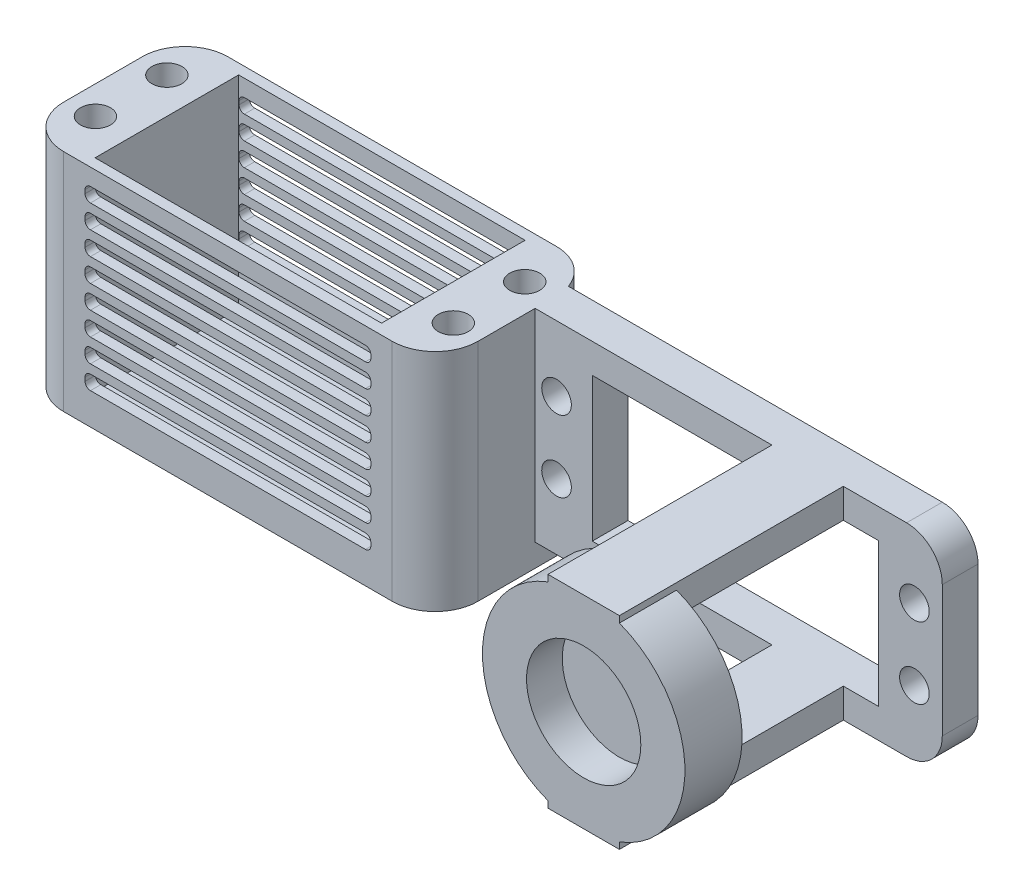
SolidWorks part; units mm, degrees
ref_plane "Front Plane" through (0, 0, 0) normal (0, 0, 1) x (1, 0, 0)
ref_plane "Top Plane" through (0, 0, 0) normal (0, 1, 0) x (1, 0, 0)
ref_plane "Right Plane" through (0, 0, 0) normal (1, 0, 0) x (0, 0, -1)
sketch "Sketch1" plane through (0, 0, 0) normal (0, 1, 0) x (1, 0, 0)
  line L0 (9.9, 0.4273) -> (50, 0.4273)
  line L1 (50, 0.4273) -> (50, -19.6727)
  line L2 (50, -19.6727) -> (9.9, -19.6727)
  line L4 (0.95, -21.1227) -> (58.95, -21.1227)
  line L5 (58.95, -21.1227) -> (58.95, 1.8773)
  line L6 (58.95, 1.8773) -> (0.95, 1.8773)
  line L8 (55, -4.6227) -> (55, -14.6227) construction
  line L9 (0.95, 1.8773) -> (0.95, -21.1227)
  line L10 (9.9, 0.4273) -> (9.9, -19.6727)
  line L11 (29.95, 0.4273) -> (29.95, -19.6727) construction
  circle A0 centre (55, -4.6227) radius 2.1
  circle A1 centre (55, -14.6227) radius 2.1
  circle A2 centre (4.9, -14.6227) radius 2.1
  circle A3 centre (4.9, -4.6227) radius 2.1
  point P13 (55, -9.6227)
  point P14 (50, -9.6227)
  point P20 (0.95, -9.6227)
  point P22 (29.95, 1.8773)
  dimension "D1" = 4.2
  dimension "D2" = 10
  dimension "D3" = 23
  dimension "D4" = 40.1
  dimension "D5" = 5
  dimension "D6" = 20.1
  dimension "D7" = 58
extrude "Boss-Extrude1" add sketch "Sketch1" along normal blind 28.35
sketch "Sketch2" plane through (58.95, 0, 0) normal (1, 0, 0) x (0, 0, -1)
  line L0 (1.8773, 28.35) -> (1.8773, 0) construction
  line L1 (-2.1227, 28.35) -> (-7.1227, 28.35)
  line L2 (-2.1227, 28.35) -> (-2.1227, 0)
  line L3 (-2.1227, 0) -> (-7.1227, 0)
  line L4 (-7.1227, 28.35) -> (-7.1227, 0)
  line L5 (-2.1227, 28.35) -> (-7.1227, 0) construction
  line L6 (-2.1227, 0) -> (-7.1227, 28.35) construction
  line L7 (-21.1227, 28.35) -> (1.8773, 28.35) construction
  point P0 (-4.6227, 14.175)
  point P5 (1.8773, 14.175)
  dimension "D1" = 4
  dimension "D2" = 5
extrude "Boss-Extrude2" add sketch "Sketch2" along normal blind 57
sketch "Sketch3" plane through (0, 0, 2.1227) normal (0, 0, -1) x (-1, 0, 0)
  line L0 (-115.95, 0) -> (-115.95, 28.35) construction
  line L1 (-66.95, 4.125) -> (-107.05, 4.125)
  line L2 (-66.95, 4.125) -> (-66.95, 24.225)
  line L3 (-66.95, 24.225) -> (-107.05, 24.225)
  line L4 (-107.05, 4.125) -> (-107.05, 24.225)
  line L5 (-66.95, 4.125) -> (-107.05, 24.225) construction
  line L6 (-66.95, 24.225) -> (-107.05, 4.125) construction
  line L8 (-58.95, 28.35) -> (-58.95, 0) construction
  point P0 (-87, 14.175)
  point P5 (-115.95, 14.175)
  dimension "D1" = 20.1
  dimension "D2" = 40.1
  dimension "D3" = 8
extrude "Cut-Extrude1" cut sketch "Sketch3" against normal through all both and the other way through all
sketch "Sketch4" plane through (0, 0, 2.1227) normal (0, 0, -1) x (-1, 0, 0)
  arc A0 (-113.8681, 18.175) -> (-113.8681, 20.175) centre (-112.05, 19.175) ccw construction
  arc A1 (-113.8681, 8.175) -> (-113.8681, 10.175) centre (-112.05, 9.175) ccw construction
  arc A2 (-60.1319, 20.175) -> (-60.1319, 18.175) centre (-61.95, 19.175) ccw construction
  arc A3 (-60.1319, 10.175) -> (-60.1319, 8.175) centre (-61.95, 9.175) ccw construction
  arc A4 (-113.8681, 18.175) -> (-113.8681, 20.175) centre (-112.05, 19.175) ccw construction
  arc A5 (-113.8681, 8.175) -> (-113.8681, 10.175) centre (-112.05, 9.175) ccw construction
  arc A6 (-60.1319, 20.175) -> (-60.1319, 18.175) centre (-61.95, 19.175) ccw construction
  arc A7 (-60.1319, 10.175) -> (-60.1319, 8.175) centre (-61.95, 9.175) ccw construction
  circle A8 centre (-61.95, 19.175) radius 2.075
  circle A9 centre (-61.95, 9.175) radius 2.075
  circle A10 centre (-112.05, 19.175) radius 2.075
  circle A11 centre (-112.05, 9.175) radius 2.075
extrude "Cut-Extrude2" cut sketch "Sketch4" against normal through all both and the other way through all
sketch "Sketch11" plane through (0, 0, 0) normal (0, -1, 0) x (1, 0, 0)
  line L1 (0.95, 21.1227) -> (58.95, 21.1227)
  line L2 (0.95, 21.1227) -> (0.95, -1.8773)
  line L3 (0.95, -1.8773) -> (58.95, -1.8773)
  line L4 (58.95, 21.1227) -> (58.95, -1.8773)
extrude "Boss-Extrude5" add sketch "Sketch11" along normal blind 3.175
fillet "Fillet1" radius 6 2 edges at (58.95, 12.5875, 21.1227) (58.95, 12.5875, -1.8773)
fillet "Fillet2" radius 5 2 edges at (115.95, 0, 4.6227) (115.95, 28.35, 4.6227)
sketch "Sketch6" plane through (0, 28.35, 0) normal (0, 1, 0) x (1, 0, 0)
  line L0 (92.1, -1.5648) -> (92.1, -8.8212) construction
  line L1 (115.95, -2.1227) -> (115.95, -7.1227) construction
  line L2 (102.1, -1.9843) -> (102.1, -5.0951) construction
  line L3 (110.95, -7.1227) -> (58.95, -7.1227) construction
  line L5 (92.1, -7.1227) -> (102.1, -7.1227)
  line L6 (92.1, -7.1227) -> (92.1, -38.4727)
  line L7 (92.1, -38.4727) -> (102.1, -38.4727)
  line L8 (102.1, -7.1227) -> (102.1, -38.4727)
  point P6 (102.1, -3.5397)
  point P7 (92.1, -7.1227)
  dimension "D1" = 10
  dimension "28" = 23.85
  dimension "D2" = 31.35
fillet "Fillet3" radius 6 2 edges at (0.95, 12.5875, 21.1227) (0.95, 12.5875, -1.8773)
extrude "Boss-Extrude3" add sketch "Sketch6" against normal up to surface (28.35 mm away) up to face at (79.6984, 0, 4.5197)
sketch "Sketch7" plane through (0, 0, 7.1227) normal (0, 0, -1) x (-1, 0, 0)
  line L1 (-92.1, 4.125) -> (-102.1, 4.125)
  line L2 (-92.1, 4.125) -> (-92.1, 24.225)
  line L3 (-92.1, 24.225) -> (-102.1, 24.225)
  line L4 (-102.1, 4.125) -> (-102.1, 24.225)
extrude "Cut-Extrude3" cut sketch "Sketch7" against normal blind 23.35
sketch "Sketch8" plane through (0, 0, 38.4727) normal (0, 0, 1) x (1, 0, 0)
  line L0 (97.1, 28.35) -> (97.1, 0) construction
  line L1 (92.1, 28.35) -> (102.1, 28.35) construction
  line L2 (102.1, 0) -> (92.1, 0) construction
  line L3 (92.1, 14.175) -> (102.1, 14.175) construction
  line L4 (92.1, 0) -> (92.1, 28.35) construction
  line L5 (102.1, 0) -> (102.1, 28.35) construction
  circle A0 centre (97.1, 14.175) radius 14.175
  point P14 (97.1, 28.35)
extrude "Boss-Extrude4" add sketch "Sketch8" against normal up to surface (8 mm away) up to face at (97.1, 14.175, 30.4727)
sketch "Sketch10" plane through (0, 0, 38.4727) normal (0, 0, 1) x (1, 0, 0)
  line L0 (111.275, 14.175) -> (82.925, 14.175) construction
  line L1 (97.1, 28.35) -> (97.1, 0)
  line L2 (92.1, 28.35) -> (102.1, 28.35) construction
  line L3 (102.1, 0) -> (92.1, 0) construction
  arc A0 (102.1, 0.9111) -> (102.1, 27.4389) centre (97.1, 14.175) ccw construction
  arc A1 (92.1, 27.4389) -> (92.1, 0.9111) centre (97.1, 14.175) ccw construction
  circle A2 centre (97.1, 14.175) radius 8
  dimension "16" = 16
extrude "Cut-Extrude4" cut sketch "Sketch10" against normal blind 5 contours A2
sketch "Sketch13" plane through (0, -3.175, 0) normal (0, -1, 0) x (1, 0, 0)
  line L0 (0.95, 15.1227) -> (0.95, 4.1227) construction
  circle A0 centre (15.05, 9.6227) radius 3
  point P2 (0.95, 9.6227)
  point P3 (0, 0)
  dimension "D2" = 6
  dimension "D1" = 14.1
extrude "Boss-Extrude6" add sketch "Sketch13" along normal blind 5
sketch "Sketch14" plane through (0, 0, -1.8773) normal (0, 0, -1) x (-1, 0, 0)
  line L0 (-6.95, 0) -> (-52.95, 0) construction
  line L1 (-6.95, -3.175) -> (-6.95, 28.35) construction
  line L2 (-52.95, 28.35) -> (-52.95, -3.175) construction
  line L3 (-6.95, -3.175) -> (-52.95, -3.175) construction
  line L4 (-10.7, 4.5) -> (-49.2, 4.5)
  line L5 (-10.7, 1.25) -> (-49.2, 1.25)
  line L6 (-9.95, 2) -> (-9.95, 2.5)
  line L7 (-10.7, 3.25) -> (-49.2, 3.25)
  line L8 (-49.95, 2) -> (-49.95, 2.5)
  line L9 (-9.95, 5.25) -> (-9.95, 5.75)
  line L10 (-10.7, 6.5) -> (-49.2, 6.5)
  line L11 (-49.95, 5.25) -> (-49.95, 5.75)
  line L12 (-10.7, 7.75) -> (-49.2, 7.75)
  line L13 (-9.95, 8.5) -> (-9.95, 9)
  line L14 (-10.7, 9.75) -> (-49.2, 9.75)
  line L15 (-49.95, 8.5) -> (-49.95, 9)
  line L16 (-10.7, 11) -> (-49.2, 11)
  line L17 (-9.95, 11.75) -> (-9.95, 12.25)
  line L18 (-10.7, 13) -> (-49.2, 13)
  line L19 (-49.95, 11.75) -> (-49.95, 12.25)
  line L20 (-10.7, 14.25) -> (-49.2, 14.25)
  line L21 (-9.95, 15) -> (-9.95, 15.5)
  line L22 (-10.7, 16.25) -> (-49.2, 16.25)
  line L23 (-49.95, 15) -> (-49.95, 15.5)
  line L24 (-10.7, 17.5) -> (-49.2, 17.5)
  line L25 (-9.95, 18.25) -> (-9.95, 18.75)
  line L26 (-10.7, 19.5) -> (-49.2, 19.5)
  line L27 (-49.95, 18.25) -> (-49.95, 18.75)
  line L28 (-10.7, 20.75) -> (-49.2, 20.75)
  line L29 (-9.95, 21.5) -> (-9.95, 22)
  line L30 (-10.7, 22.75) -> (-49.2, 22.75)
  line L31 (-49.95, 21.5) -> (-49.95, 22)
  line L32 (-10.7, 24) -> (-49.2, 24)
  line L33 (-9.95, 24.75) -> (-9.95, 25.25)
  line L34 (-10.7, 26) -> (-49.2, 26)
  line L35 (-49.95, 24.75) -> (-49.95, 25.25)
  arc A0 (-49.2, 1.25) -> (-49.95, 2) centre (-49.2, 2) cw
  arc A1 (-49.2, 3.25) -> (-49.95, 2.5) centre (-49.2, 2.5) ccw
  arc A2 (-9.95, 2.5) -> (-10.7, 3.25) centre (-10.7, 2.5) ccw
  arc A3 (-10.7, 1.25) -> (-9.95, 2) centre (-10.7, 2) ccw
  arc A4 (-49.2, 4.5) -> (-49.95, 5.25) centre (-49.2, 5.25) cw
  arc A5 (-49.2, 6.5) -> (-49.95, 5.75) centre (-49.2, 5.75) ccw
  arc A6 (-9.95, 5.75) -> (-10.7, 6.5) centre (-10.7, 5.75) ccw
  arc A7 (-10.7, 4.5) -> (-9.95, 5.25) centre (-10.7, 5.25) ccw
  arc A8 (-49.2, 7.75) -> (-49.95, 8.5) centre (-49.2, 8.5) cw
  arc A9 (-49.2, 9.75) -> (-49.95, 9) centre (-49.2, 9) ccw
  arc A10 (-9.95, 9) -> (-10.7, 9.75) centre (-10.7, 9) ccw
  arc A11 (-10.7, 7.75) -> (-9.95, 8.5) centre (-10.7, 8.5) ccw
  arc A12 (-49.2, 11) -> (-49.95, 11.75) centre (-49.2, 11.75) cw
  arc A13 (-49.2, 13) -> (-49.95, 12.25) centre (-49.2, 12.25) ccw
  arc A14 (-9.95, 12.25) -> (-10.7, 13) centre (-10.7, 12.25) ccw
  arc A15 (-10.7, 11) -> (-9.95, 11.75) centre (-10.7, 11.75) ccw
  arc A16 (-49.2, 14.25) -> (-49.95, 15) centre (-49.2, 15) cw
  arc A17 (-49.2, 16.25) -> (-49.95, 15.5) centre (-49.2, 15.5) ccw
  arc A18 (-9.95, 15.5) -> (-10.7, 16.25) centre (-10.7, 15.5) ccw
  arc A19 (-10.7, 14.25) -> (-9.95, 15) centre (-10.7, 15) ccw
  arc A20 (-49.2, 17.5) -> (-49.95, 18.25) centre (-49.2, 18.25) cw
  arc A21 (-49.2, 19.5) -> (-49.95, 18.75) centre (-49.2, 18.75) ccw
  arc A22 (-9.95, 18.75) -> (-10.7, 19.5) centre (-10.7, 18.75) ccw
  arc A23 (-10.7, 17.5) -> (-9.95, 18.25) centre (-10.7, 18.25) ccw
  arc A24 (-49.2, 20.75) -> (-49.95, 21.5) centre (-49.2, 21.5) cw
  arc A25 (-49.2, 22.75) -> (-49.95, 22) centre (-49.2, 22) ccw
  arc A26 (-9.95, 22) -> (-10.7, 22.75) centre (-10.7, 22) ccw
  arc A27 (-10.7, 20.75) -> (-9.95, 21.5) centre (-10.7, 21.5) ccw
  arc A28 (-49.2, 24) -> (-49.95, 24.75) centre (-49.2, 24.75) cw
  arc A29 (-49.2, 26) -> (-49.95, 25.25) centre (-49.2, 25.25) ccw
  arc A30 (-9.95, 25.25) -> (-10.7, 26) centre (-10.7, 25.25) ccw
  arc A31 (-10.7, 24) -> (-9.95, 24.75) centre (-10.7, 24.75) ccw
  point P12 (-29.95, 1.25)
  point P13 (-29.95, 0)
  point P17 (-49.95, 1.25)
  point P22 (-9.95, 3.25)
  point P25 (-9.95, 1.25)
  point P30 (-29.95, 4.5)
  point P31 (-29.95, 3.25)
  point P44 (-29.95, 7.75)
  point P45 (-29.95, 6.5)
  point P58 (-29.95, 11)
  point P59 (-29.95, 9.75)
  point P72 (-29.95, 14.25)
  point P73 (-29.95, 13)
  point P86 (-29.95, 17.5)
  point P87 (-29.95, 16.25)
  point P100 (-29.95, 20.75)
  point P101 (-29.95, 19.5)
  point P114 (-29.95, 24)
  point P115 (-29.95, 22.75)
  dimension "D5" = 0.75
  dimension "D1" = 3.175
  dimension "D2" = 2
  dimension "D3" = 1.25
  dimension "D4" = 40
  dimension "D7" = 1.25
  dimension "D6" = 8
extrude "Cut-Extrude5" cut sketch "Sketch14" against normal through all both and the other way through all
